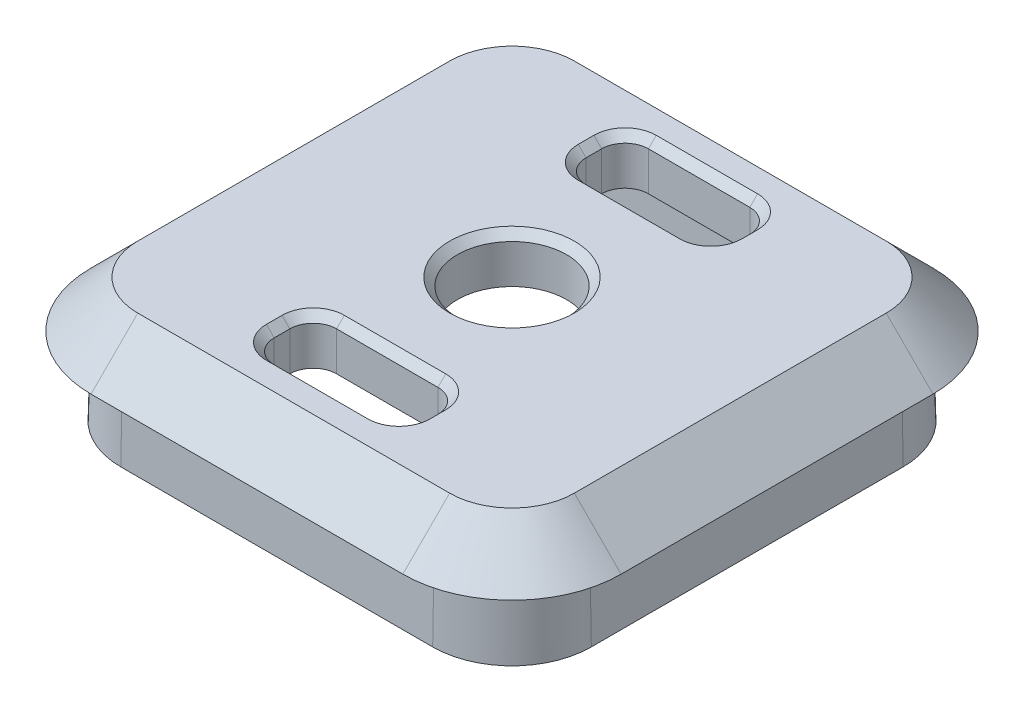
SolidWorks part; units mm, degrees
ref_plane "Alzado" through (0, 0, 0) normal (0, 0, 1) x (1, 0, 0)
ref_plane "Planta" through (0, 0, 0) normal (0, 1, 0) x (1, 0, 0)
ref_plane "Vista lateral" through (0, 0, 0) normal (1, 0, 0) x (0, 0, -1)
sketch "Croquis1" plane through (0, 0, 0) normal (0, 1, 0) x (1, 0, 0)
  line L1 (-17, 17) -> (17, 17)
  line L2 (-17, 17) -> (-17, -17)
  line L3 (-17, -17) -> (17, -17)
  line L4 (17, 17) -> (17, -17)
  line L5 (-17, 17) -> (17, -17) construction
  line L6 (-17, -17) -> (17, 17) construction
  point P0 (0, 0)
  dimension "D1" = 34
  dimension "D2" = 34
extrude "Saliente-Extruir1" add sketch "Croquis1" along normal blind 3
fillet "Redondeo1" radius 7 4 edges at (-17, 1.5, -17) (-17, 1.5, 17) (17, 1.5, -17) (17, 1.5, 17)
chamfer "Chaflán1" distance 3 angle 45 8 edges at (17, 3, 0) (14.9497, 3, -14.9497) (14.9497, 3, 14.9497) (0, 3, -17) (0, 3, 17) (-14.9497, 3, -14.9497) (-14.9497, 3, 14.9497) (-17, 3, 0)
sketch "Croquis2" plane through (0, 3, 0) normal (0, 1, 0) x (1, 0, 0)
  line L3 (-4.75, 12) -> (4.75, 12)
  line L4 (-4.75, 12) -> (-4.75, 8)
  line L5 (-4.75, 8) -> (4.75, 8)
  line L6 (4.75, 12) -> (4.75, 8)
  line L7 (-4.75, 12) -> (4.75, 8) construction
  line L8 (-4.75, 8) -> (4.75, 12) construction
  point P0 (0, 10)
  dimension "D2" = 9.5
  dimension "D3" = 10
  dimension "D1" = 4
extrude "Cortar-Extruir1" cut sketch "Croquis2" against normal through all
fillet "Redondeo2" radius 1.5 4 edges at (-4.75, 1.5, -8) (4.75, 1.5, -8) (4.75, 1.5, -12) (-4.75, 1.5, -12)
chamfer "Chaflán2" distance 0.5 angle 45 8 edges at (4.3107, 3, -11.5607) (4.75, 3, -10) (4.3107, 3, -8.4393) (0, 3, -8) (-4.3107, 3, -8.4393) (-4.75, 3, -10) (-4.3107, 3, -11.5607) (0, 3, -12)
sketch "Croquis6" plane through (0, 0, 0) normal (0, 0, 1) x (1, 0, 0)
  line L0 (-15, 0) -> (-15, -2)
  line L1 (-17, 0) -> (-10, 0) construction
  line L4 (-15.5, -2.182) -> (-15.5, -3)
  line L5 (-15.5, -3) -> (-13, -3)
  line L6 (-13, -3) -> (-13, 0)
  line L7 (-15, 0) -> (-13, 0)
  line L8 (-15.5, -2.182) -> (-15, -2)
  dimension "D1" = 2
  dimension "D2" = 0.5
  dimension "D3" = 110
  dimension "D4" = 1
  dimension "D5" = 2
  dimension "D6" = 3
sketch "Croquis8" plane through (0, 0, 0) normal (0, -1, 0) x (1, 0, 0)
  line L0 (-13, 10) -> (-13, -10)
  line L1 (-10, 15) -> (10, 15)
  line L2 (-15, 10) -> (-15, -10)
  line L3 (-10, -15) -> (10, -15)
  line L4 (15, 10) -> (15, -10)
  line L5 (-15, 15) -> (15, -15) construction
  line L6 (-15, -15) -> (15, 15) construction
  line L7 (-10, -13) -> (10, -13)
  line L8 (13, 10) -> (13, -10)
  line L9 (-10, 13) -> (10, 13)
  arc A0 (10, 15) -> (15, 10) centre (10, 10) cw
  arc A1 (15, -10) -> (10, -15) centre (10, -10) cw
  arc A2 (-10, -15) -> (-15, -10) centre (-10, -10) cw
  arc A3 (-10, 15) -> (-15, 10) centre (-10, 10) ccw
  arc A4 (-10, -13) -> (-13, -10) centre (-10, -10) cw
  arc A5 (13, -10) -> (10, -13) centre (10, -10) cw
  arc A6 (10, 13) -> (13, 10) centre (10, 10) cw
  arc A7 (-10, 13) -> (-13, 10) centre (-10, 10) ccw
  point P0 (0, 0)
  dimension "D3" = 5
  dimension "D1" = 30
  dimension "D2" = 30
  dimension "D4" = 2
extrude "Saliente-Extruir2" add sketch "Croquis8" along normal blind 5 draft 1 draft outward yes
sketch "Croquis9" plane through (0, 3, 0) normal (0, 1, 0) x (1, 0, 0)
  circle A0 centre (0, 0) radius 3.5
  dimension "D1" = 7
extrude "Cortar-Extruir2" cut sketch "Croquis9" against normal through all
chamfer "Chaflán3" distance 0.5 angle 45 1 edges at (0, 3, 3.5)
mirror "Simetría1" about plane through (0, 0, 0) normal (0, 0, 1) of "Chaflán2", "Redondeo2", "Cortar-Extruir1"
sketch3d "Croquis3D1"
  line L0 (0, 0, 0) -> (0, 7.4311, 0)
